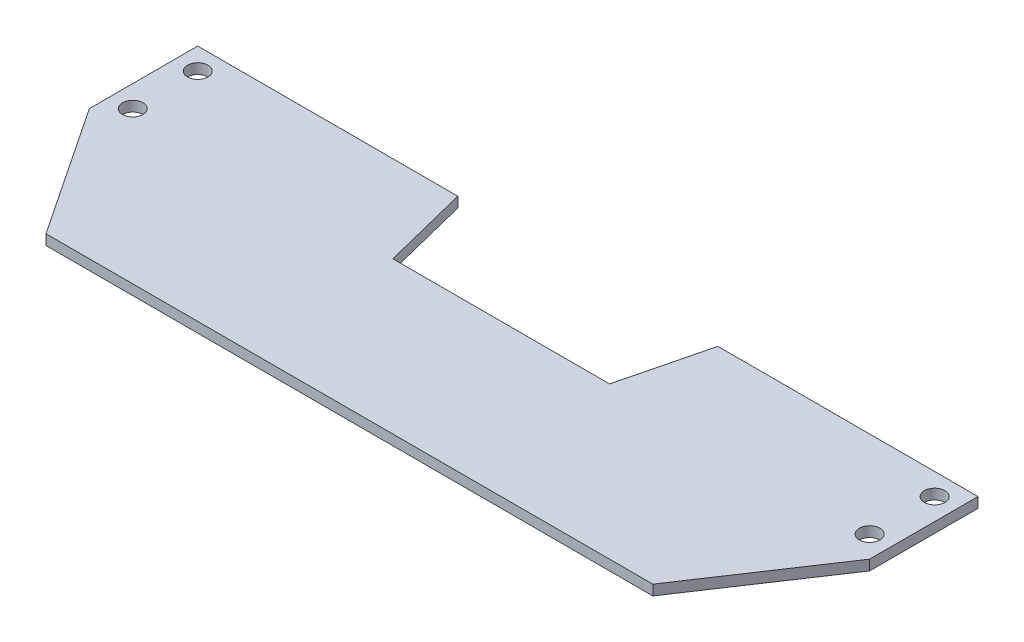
SolidWorks part; units mm, degrees
material "Ti-6Al-4VSolution treated and aged (SS)"
ref_plane "Front Plane" through (0, 0, 0) normal (0, 0, 1) x (1, 0, 0)
ref_plane "Top Plane" through (0, 0, 0) normal (0, 1, 0) x (1, 0, 0)
ref_plane "Right Plane" through (0, 0, 0) normal (1, 0, 0) x (0, 0, -1)
sketch "Sketch1" plane through (0, 0, 0) normal (0, 1, 0) x (1, 0, 0)
  line L0 (-57.15, 1.5875) -> (-44.45, -17.4625)
  line L1 (-44.45, -17.4625) -> (44.45, -17.4625)
  line L2 (-57.15, 1.5875) -> (-57.15, 17.4625)
  line L3 (-57.15, 17.4625) -> (-19.05, 17.4625)
  line L4 (57.15, 1.5875) -> (57.15, 17.4625)
  line L5 (-57.15, -17.4625) -> (57.15, 17.4625) construction
  line L6 (-57.15, 17.4625) -> (57.15, -17.4625) construction
  line L7 (0, 17.4625) -> (0, -17.4625) construction
  line L8 (57.15, 1.5875) -> (44.45, -17.4625)
  line L9 (-57.15, -17.4625) -> (-57.15, 1.5875) construction
  line L10 (-57.15, -17.4625) -> (-44.45, -17.4625) construction
  line L11 (44.45, -17.4625) -> (57.15, -17.4625) construction
  line L12 (57.15, -17.4625) -> (57.15, 1.5875) construction
  line L13 (-19.05, 17.4625) -> (-15.875, 4.7625)
  line L14 (-15.875, 4.7625) -> (15.875, 4.7625)
  line L15 (19.05, 17.4625) -> (15.875, 4.7625)
  line L16 (19.05, 17.4625) -> (57.15, 17.4625)
  line L17 (-19.05, 17.4625) -> (0, 17.4625) construction
  line L18 (0, 17.4625) -> (19.05, 17.4625) construction
  point P0 (0, 0)
  point P16 (0, 4.7625)
  dimension "D1" = 114.3
  dimension "D2" = 34.925
  dimension "D3" = 12.7
  dimension "D4" = 19.05
  dimension "D5" = 38.1
  dimension "D6" = 31.75
  dimension "D7" = 12.7
extrude "Boss-Extrude1" add sketch "Sketch1" along normal blind 1.4985
sketch "Sketch2" plane through (0, 1.4985, 0) normal (0, 1, 0) x (1, 0, 0)
  line L0 (0, 4.7625) -> (0, -17.4625) construction
  line L1 (-19.05, 17.4625) -> (-57.15, 17.4625) construction
  line L2 (-44.45, -17.4625) -> (44.45, -17.4625) construction
  line L3 (-57.15, 17.4625) -> (-57.15, 1.5875) construction
  line L4 (-53.975, 14.2875) -> (-53.975, 4.7625) construction
  line L5 (15.875, 4.7625) -> (-15.875, 4.7625) construction
  circle A0 centre (-53.975, 14.2875) radius 1.5
  circle A1 centre (-53.975, 4.7625) radius 1.5
  circle A2 centre (53.975, 4.7625) radius 1.5
  circle A3 centre (53.975, 14.2875) radius 1.5
  point P16 (0, 0)
  point P17 (0, 11.1125)
  dimension "D1" = 3
  dimension "D2" = 3.175
  dimension "D3" = 3.175
  dimension "D4" = 9.525
extrude "Cut-Extrude1" cut sketch "Sketch2" against normal through all
